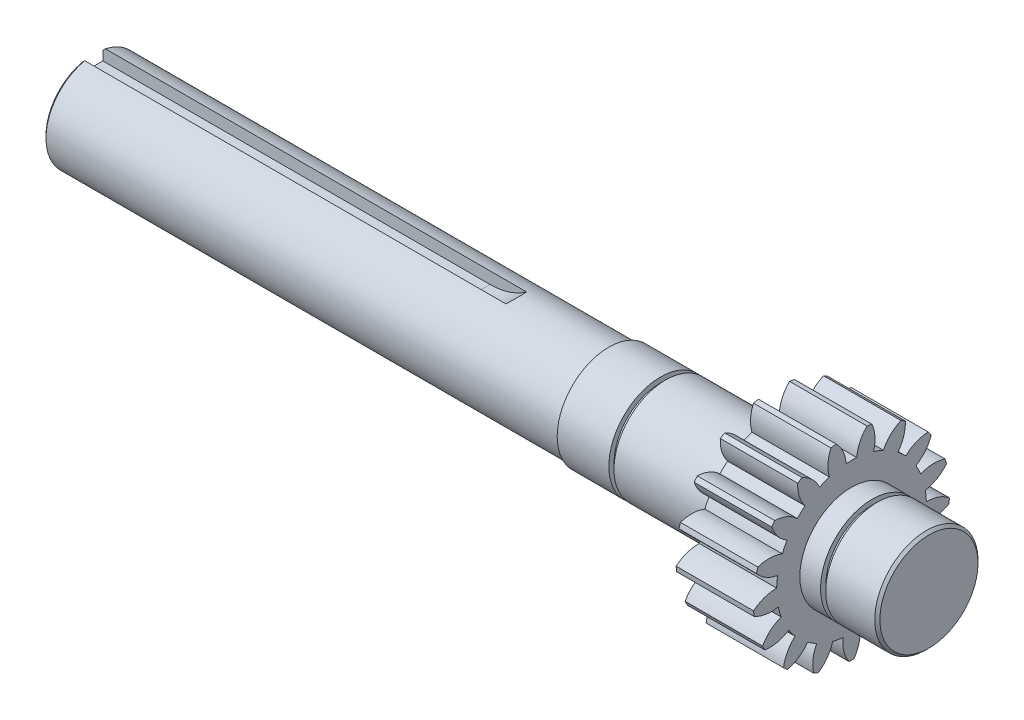
SolidWorks part; units mm, degrees
ref_plane "Plane1" through (0, 0, 0) normal (0, 0, 1) x (1, 0, 0)
ref_plane "Plane2" through (0, 0, 0) normal (0, 1, 0) x (1, 0, 0)
ref_plane "Plane3" through (0, 0, 0) normal (1, 0, 0) x (0, 0, -1)
other "Configuration Table"
sketch "HoldingSke" plane through (0, 0, 0) normal (0, 1, 0) x (1, 0, 0)
  line L0 (0, 0) -> (0.4782, -0.1462)
  line L1 (-15, 0) -> (100, 0) construction
  line L2 (0, 0) -> (-2.1039, 2.3779)
  line L3 (0, 0) -> (-11.863, 4.5341)
  line L4 (0, 0) -> (8.2586, 2.5249)
  line L5 (0, 0) -> (-46.8476, -17.4728)
  line L6 (0, 0) -> (-12.4344, -8.3896)
  line L7 (-2.1039, 2.3779) -> (8.6586, 51.2059)
  line L8 (-76.2, 54.61) -> (-76.1, 54.61)
  line L9 (-71.009, 38.7566) -> (-53.1078, 45.2721)
  line L10 (-76.2, 71.12) -> (104.1128, 71.12)
  line L11 (0, 0) -> (-15, 0)
  line L12 (-76.2, 101.6) -> (-76.133, 101.6)
  line L13 (24.9733, 27.94) -> (52.9518, 28.4284)
  line L14 (24.9733, 27.94) -> (24.9743, 27.94)
  line L15 (24.9733, 27.94) -> (100.4006, 29.5858)
  line L16 (-63.627, -2) -> (-12.827, -2)
  circle A0 centre (0, 0) radius 0.4
  circle A1 centre (0, 0) radius 14.499
  circle A2 centre (0, 0) radius 37.5
  circle A3 centre (0, 0) radius 0.4
  dimension "Num_teeth" = 17
  dimension "Pitch_radius" = 180.3128
  dimension "Width" = 15
  dimension "Thickness" = 15
sketch "BasProSke" plane through (0, 0, 0) normal (0, 1, 0) x (1, 0, 0)
  line L0 (-10, 0) -> (60, 0) construction
  line L1 (0, 0) -> (0, 19)
  line L2 (0, 0) -> (15, 0)
  line L3 (15, 0) -> (15, 19)
  line L4 (15, 19) -> (0, 19)
  dimension "Thickness" = 15
  dimension "Diameter" = 38
revolve "Base-Revolve" add sketch "BasProSke" angle 360 about L0
sketch "TooCutSke" plane through (0, 0, 0) normal (1, 0, 0) x (0, 0, -1)
  line L1 (0, 0) -> (0, 107) construction
  line L2 (0, 0) -> (-1.6857, 16.9162) construction
  line L3 (0, 0) -> (-6.2247, 33.2991) construction
  line L4 (-1.6857, 16.9162) -> (-3.1123, 16.6495) construction
  arc A0 (1.0204, 14.4631) -> (-1.0204, 14.4631) centre (0, 0) ccw
  arc A1 (3.0261, 18.7832) -> (-3.0261, 18.7832) centre (0, 0) ccw
  circle A2 centre (0, 0) radius 17 construction
  circle A3 centre (0, 0) radius 15.9748 construction
  arc A4 (-1.0204, 14.4631) -> (-3.0261, 18.7832) centre (-7.8003, 13.9409) ccw
  arc A5 (3.0261, 18.7832) -> (1.0204, 14.4631) centre (7.8003, 13.9409) ccw
extrude "ToothCut" cut sketch "TooCutSke" along normal through all
fillet "Breaks" [suppressed] radius 0.04 tangent propagation no
fillet "RootFillets" [suppressed] radius 0.501
pattern_circular "TeethCuts" count 17 every 21.176 about axis through (-10, 0, 0) along (1, 0, 0) of "ToothCut", "RootFillets", "Breaks"
sketch "HubNeaOneSke" plane through (0, 0, 0) normal (-1, 0, 0) x (0, 0, 1)
  circle A0 centre (0, 0) radius 14.499
  dimension "Diameter" = 28.998
extrude "HubNearOne" [suppressed] add sketch "HubNeaOneSke" along normal blind 35.0001
sketch "HubNeaBotSke" plane through (0, 0, 0) normal (-1, 0, 0) x (0, 0, 1)
  circle A0 centre (0, 0) radius 14.499
  dimension "Diameter" = 28.998
extrude "HubNearBoth" [suppressed] add sketch "HubNeaBotSke" along normal blind 17.5
ref_plane "FarPln" through (15, 0, 0) normal (1, 0, 0) x (0, 0, -1)
sketch "HubFarSke" plane through (15, 0, 0) normal (1, 0, 0) x (0, 0, -1)
  circle A0 centre (0, 0) radius 14.499
  dimension "Diameter" = 28.998
extrude "HubFar" [suppressed] add sketch "HubFarSke" along normal blind 17.5
sketch "BorSke" plane through (0, 0, 0) normal (1, 0, 0) x (0, 0, -1)
  circle A0 centre (0, 0) radius 0.4
  dimension "Diameter" = 0.8
extrude "Bore" cut sketch "BorSke" along normal mid plane 100.0001
sketch "KeySke" plane through (0, 0, 0) normal (1, 0, 0) x (0, 0, -1)
  line L0 (-0.05, 0) -> (-0.05, 0.5)
  line L1 (-0.05, 0.5) -> (0.05, 0.5)
  line L2 (0.05, 0.5) -> (0.05, 0)
  line L3 (0, 0) -> (0, 34) construction
  line L4 (-0.05, 0) -> (0.05, 0)
extrude "Keyway" [suppressed] cut sketch "KeySke" along normal mid plane 100.0001
pattern_circular "Keyway2" [suppressed] count 2 every 90 about axis through (-10, 0, 0) along (1, 0, 0)
sketch "Sketch1" plane through (15, 0, 0) normal (1, 0, 0) x (0, 0, -1)
  circle A0 centre (0, 0) radius 10
  dimension "D1" = 20
extrude "Boss-Extrude1" add sketch "Sketch1" along normal blind 15
sketch "Sketch2" plane through (0, 0, 0) normal (-1, 0, 0) x (0, 0, 1)
  circle A0 centre (0, 0) radius 10
  circle A1 centre (0, 0) radius 9.5
  dimension "D1" = 20
  dimension "D2" = 19
extrude "Boss-Extrude2" add sketch "Sketch2" along normal blind 32 contours A0
extrude "Boss-Extrude3" add sketch "Sketch2<3>" along normal blind 100 from surface contours A1 starting at face at (-32, 0, 10)
sketch "Sketch2<3>" plane through (0, 0, 0) normal (-1, 0, 0) x (0, 0, 1) same geometry as "Sketch2"
sketch "Sketch3" plane through (0, 0, 0) normal (0, 0, 1) x (1, 0, 0)
  line L0 (-132, 9.5) -> (-132, 7)
  line L1 (-132, 9.5) -> (-132, -9.5) construction
  line L2 (-132, 7) -> (-57, 7)
  line L3 (-32, 9.5) -> (-132, 9.5) construction
  line L4 (-49.6686, 9.5) -> (-132, 9.5)
  line L5 (-139.7781, 0) -> (0, 0) construction
  line L6 (0, 10) -> (0, -10) construction
  arc A0 (-57, 7) -> (-49.6686, 9.5) centre (-57, 19) ccw
  dimension "D3" = 12
  dimension "D1" = 7
  dimension "D2" = 75
extrude "Cut-Extrude1" cut sketch "Sketch3" against normal mid plane 4
sketch "Sketch4" plane through (0, 0, 0) normal (0, 0, 1) x (1, 0, 0)
  line L0 (30, 10) -> (15, 10) construction
  line L1 (20, 10) -> (19, 10)
  line L2 (20, 10) -> (20, 9)
  line L3 (20, 9) -> (19, 9)
  line L4 (19, 10) -> (19, 9)
  line L5 (0, 10) -> (-32, 10) construction
  line L6 (-21, 10) -> (-22, 10)
  line L7 (-21, 10) -> (-21, 9)
  line L8 (-21, 9) -> (-22, 9)
  line L9 (-22, 10) -> (-22, 9)
  line L10 (0, 0) -> (-25.5125, 0) construction
  line L11 (0, 10) -> (0, -10) construction
  line L12 (30, -10) -> (30, 10) construction
  line L13 (0, 11.0514) -> (0, 7.3601) construction
  point P16 (-21.5, 9)
  dimension "D1" = 1
  dimension "D2" = 18
  dimension "D3" = 18
  dimension "D4" = 1
  dimension "D5" = 10
  dimension "D6" = 21
revolve "Cut-Revolve1" cut sketch "Sketch4" angle 360 about L10
chamfer "Chamfer1" distance 0.5 angle 45 2 edges at (-132, -9.5, 0) (30, 0, -10)
equation "' \"Module@HoldingSke\" = 6.35"
equation "' \"Num_teeth@HoldingSke\" = 12"
equation "' \"Ap@HoldingSke\" =  20"
equation "' \"Ap@HoldingSke\" = 20"
equation "' \"Width@HoldingSke\" = 0.5 * 25.4"
equation "' \"Hub_dia@HoldingSke\"= 1 * 25.4"
equation "' \"Hub_dia@HoldingSke\" = 1 * 25.4"
equation "' \"Overall_len@HoldingSke\" = 1.0 * 25.4"
equation "' \"Bore@HoldingSke\" = 0.75 * 25.4"
equation "' \"T_dim@HoldingSke\" = 0.1 * 25.4"
equation "' \"Width@KeySke\" = 0.25 * 25.4"
equation "' \"Show_teeth@HoldingSke\" = 13"
equation "' \"Backlash@HoldingSke\" = 0.009 * 25.4"
equation "' \"Addendum_fac@HoldingSke\" = 1.0"
equation "' \"Dedendum_fac@HoldingSke\" = 1.25"
equation "' \"Dedendum_add@HoldingSke\" = 0.00005 * 25.4"
equation "' \"Clearance_fac@HoldingSke\" = 0.25"
equation "\"Pitch@HoldingSke\" = 1 / \"Module@HoldingSke\""
equation "\"Overcut_dia@TooCutSke\" = (\"Num_teeth@HoldingSke\" + 2 * \"Addendum_fac@HoldingSke\") / \"Pitch@HoldingSke\" + 0.002 * 25.4"
equation "\"Pitch_dia@TooCutSke\" = \"Num_teeth@HoldingSke\" / \"Pitch@HoldingSke\""
equation "\"Base_dia@TooCutSke\" = \"Num_teeth@HoldingSke\" / \"Pitch@HoldingSke\" * cos((\"Ap@HoldingSke\"  * 3.14159265 / 180))"
equation "\"Root_dia@TooCutSke\" = (\"Num_teeth@HoldingSke\" + 2) / \"Pitch@HoldingSke\" - 2 * (\"Addendum_fac@HoldingSke\" + \"Dedendum_fac@HoldingSke\") / \"Pitch@HoldingSke\" - \"Dedendum_add@HoldingSke\" * 2"
equation "\"Half_ang@TooCutSke\" = 180 / \"Num_teeth@HoldingSke\""
equation "\"Half_CT@TooCutSke\" = \"Num_teeth@HoldingSke\" / \"Pitch@HoldingSke\" * sin((3.14159265 / 2 / \"Num_teeth@HoldingSke\")) / 2 - 7 * \"Backlash@HoldingSke\" / 4"
equation "\"Flank_rad@TooCutSke\" = \"Num_teeth@HoldingSke\" / \"Pitch@HoldingSke\" / 5"
equation "\"Radius@RootFillets\" = \"Clearance_fac@HoldingSke\" / \"Pitch@HoldingSke\" + \"Dedendum_add@HoldingSke\""
equation "\"Break_rad@Breaks\" = 0.02 / \"Pitch@HoldingSke\""
equation "\"Thickness@HoldingSke\" = \"Width@HoldingSke\""
equation "\"OAL@HoldingSke\" = \"Thickness@HoldingSke\""
equation "\"MHD@HoldingSke\" = (\"Num_teeth@HoldingSke\" + 2) / \"Pitch@HoldingSke\" - 2 * (\"Addendum_fac@HoldingSke\" + \"Dedendum_fac@HoldingSke\")  / \"Pitch@HoldingSke\" - \"Dedendum_add@HoldingSke\" * 2"
equation "\"MBD@HoldingSke\" = (\"Num_teeth@HoldingSke\" + 2) / \"Pitch@HoldingSke\" - 2 * (\"Addendum_fac@HoldingSke\" + \"Dedendum_fac@HoldingSke\")  / \"Pitch@HoldingSke\" - \"Dedendum_add@HoldingSke\" * 2 - 0.002 * 25.4"
equation "\"MHD@HoldingSke\" = ((sgn( \"MHD@HoldingSke\" - \"Hub_dia@HoldingSke\" )-1)*( \"MHD@HoldingSke\" - \"Hub_dia@HoldingSke\" ))/-2+ \"Hub_dia@HoldingSke\""
equation "\"MBD@HoldingSke\" = ((sgn( \"MBD@HoldingSke\" - \"Bore@HoldingSke\" )-1)*( \"MBD@HoldingSke\" - \"Bore@HoldingSke\" ))/-2+ \"Bore@HoldingSke\""
equation "\"OAL@HoldingSke\" = ((sgn( \"OAL@HoldingSke\" - \"Overall_len@HoldingSke\" )+1)*( \"OAL@HoldingSke\" - \"Overall_len@HoldingSke\" ))/2 + \"Overall_len@HoldingSke\" + 0.000002 * 25.4"
equation "\"Num_teeth@TeethCuts\" = int( \"Show_teeth@HoldingSke\" ) + 1"
equation "\"Num_teeth@TeethCuts\" = ((sgn( \"Num_teeth@TeethCuts\" - \"Num_teeth@HoldingSke\" )-1)*( \"Num_teeth@TeethCuts\" - \"Num_teeth@HoldingSke\" ))/-2+ \"Num_teeth@HoldingSke\""
equation "\"Num_teeth@TeethCuts\" = ((sgn( \"Num_teeth@TeethCuts\" - 2.0)+1)*( \"Num_teeth@TeethCuts\" - 2.0))/2 +2.0"
equation "\"Angle@TeethCuts\" = 360.0 / \"Num_teeth@HoldingSke\""
equation "\"Diameter@BasProSke\" = (\"Num_teeth@HoldingSke\" + 2 * \"Addendum_fac@HoldingSke\") / \"Pitch@HoldingSke\""
equation "\"Thickness@BasProSke\"  = \"Thickness@HoldingSke\""
equation "' \"Fillet_rad@BasProSke\" =  \"Thickness@HoldingSke\" * 0.05"
equation "' \"Fillet_rad@BasProSke\" = \"Thickness@HoldingSke\" * 0.05"
equation "\"MHD@HoldingSke\" = ((sgn( \"MHD@HoldingSke\" - \"Root_dia@TooCutSke\" )-1)*( \"MHD@HoldingSke\" - \"Root_dia@TooCutSke\" ))/-2+ \"Root_dia@TooCutSke\""
equation "\"Diameter@HubNeaOneSke\" = \"MHD@HoldingSke\""
equation "\"Length@HubNearOne\" = \"OAL@HoldingSke\" - \"Thickness@BasProSke\""
equation "\"Diameter@HubNeaBotSke\" = \"MHD@HoldingSke\""
equation "\"Length@HubNearBoth\" = ( \"OAL@HoldingSke\" - \"Thickness@BasProSke\" ) / 2.0"
equation "\"Thickness@FarPln\" = \"Thickness@BasProSke\""
equation "\"Diameter@HubFarSke\" = \"MHD@HoldingSke\""
equation "\"Length@HubFar\" = ( \"OAL@HoldingSke\" - \"Thickness@BasProSke\" ) / 2.0"
equation "\"Diameter@BorSke\" = \"MBD@HoldingSke\""
equation "\"D1@Bore\" = \"OAL@HoldingSke\" * 2.0"
equation "\"D1@Keyway\" = \"OAL@HoldingSke\" * 2.0"
equation "\"Offset@KeySke\" = \"T_dim@HoldingSke\" + \"MBD@HoldingSke\" / 2.0"
